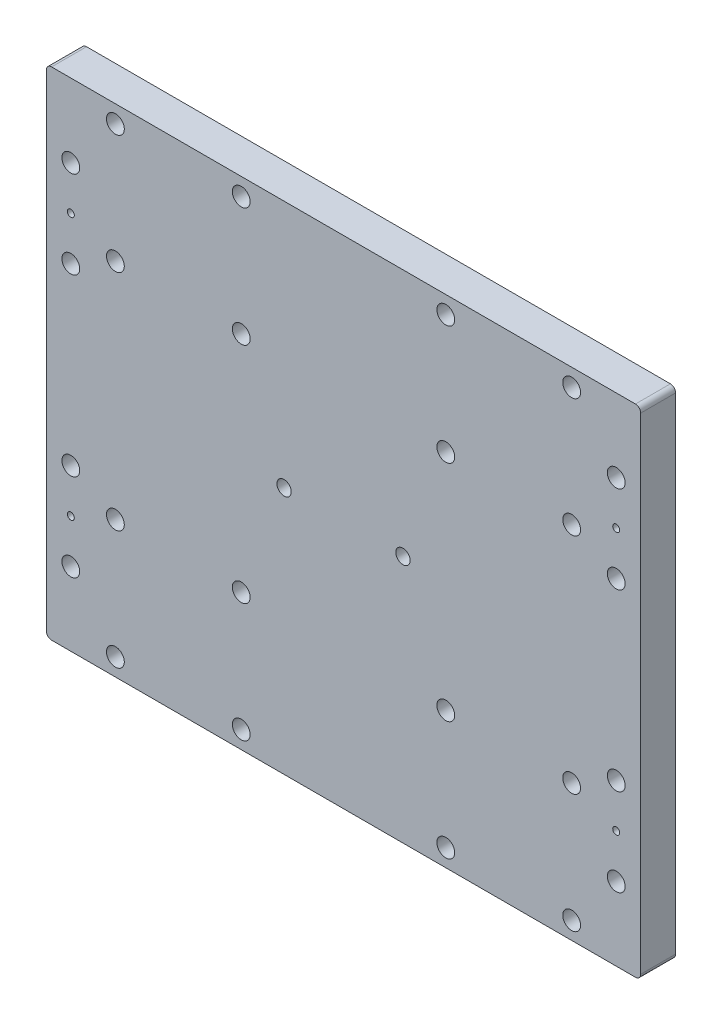
SolidWorks part; units mm, degrees
ref_plane "Front Plane" through (0, 0, 0) normal (0, 0, 1) x (1, 0, 0)
ref_plane "Top Plane" through (0, 0, 0) normal (0, 1, 0) x (1, 0, 0)
ref_plane "Right Plane" through (0, 0, 0) normal (1, 0, 0) x (0, 0, -1)
sketch "Sketch1" plane through (0, 0, 0) normal (0, 0, 1) x (1, 0, 0)
  line L1 (85, -71) -> (-85, -71)
  line L2 (85, -71) -> (85, 71)
  line L3 (85, 71) -> (-85, 71)
  line L4 (-85, -71) -> (-85, 71)
  line L5 (85, -71) -> (-85, 71) construction
  line L6 (85, 71) -> (-85, -71) construction
  point P0 (0, 0)
  dimension "D1" = 170
  dimension "D2" = 142
extrude "Boss-Extrude1" add sketch "Sketch1" along normal mid plane 10
sketch "Sketch2" plane through (0, 0, 5) normal (0, 0, 1) x (1, 0, 0)
  line L0 (-65.25, 71) -> (-65.25, -71) construction
  line L1 (65.25, -71) -> (65.25, 71) construction
  line L2 (-29.25, 71) -> (-29.25, -71) construction
  line L3 (29.25, -71) -> (29.25, 71) construction
  line L4 (70.6711, 66) -> (-71.3289, 66) construction
  line L5 (-71.3289, -66) -> (70.6711, -66) construction
  line L6 (70.6711, 32) -> (-71.3289, 32) construction
  line L7 (-71.3289, -32) -> (70.6711, -32) construction
  line L8 (85, 71) -> (-85, 71) construction
  line L9 (-85, -71) -> (85, -71) construction
  line L10 (-85, 71) -> (-85, -71) construction
  line L11 (85, -71) -> (85, 71) construction
  circle A0 centre (-65.25, 66) radius 2.55
  circle A1 centre (-29.25, 66) radius 2.55
  circle A2 centre (-29.25, 32) radius 2.55
  circle A3 centre (-65.25, 32) radius 2.55
  circle A4 centre (65.25, 66) radius 2.55
  circle A5 centre (65.25, 32) radius 2.55
  circle A6 centre (29.25, 32) radius 2.55
  circle A7 centre (29.25, 66) radius 2.55
  circle A8 centre (-65.25, -32) radius 2.55
  circle A9 centre (-29.25, -32) radius 2.55
  circle A10 centre (-29.25, -66) radius 2.55
  circle A11 centre (-65.25, -66) radius 2.55
  circle A12 centre (29.25, -32) radius 2.55
  circle A13 centre (65.25, -32) radius 2.55
  circle A14 centre (65.25, -66) radius 2.55
  circle A15 centre (29.25, -66) radius 2.55
  dimension "D1" = 5.1
  dimension "D2" = 5.1
  dimension "D3" = 5.1
  dimension "D4" = 5.1
  dimension "D5" = 5.1
  dimension "D6" = 5.1
  dimension "D7" = 5.1
  dimension "D8" = 5.1
  dimension "D9" = 5.1
  dimension "D10" = 5.1
  dimension "D11" = 5.1
  dimension "D12" = 5.1
  dimension "D13" = 5.1
  dimension "D14" = 5.1
  dimension "D15" = 5.1
  dimension "D16" = 5.1
  dimension "D17" = 5
  dimension "D18" = 5
  dimension "D19" = 34
  dimension "D20" = 34
  dimension "D21" = 36
  dimension "D22" = 36
  dimension "D23" = 19.75
  dimension "D24" = 19.75
extrude "Cut-Extrude1" cut sketch "Sketch2" against normal through all
sketch "Sketch4" plane through (0, 0, 5) normal (0, 0, 1) x (1, 0, 0)
  line L3 (-17, 0) -> (17, 0) construction
  circle A0 centre (-17, 0) radius 2.05
  circle A3 centre (17, 0) radius 2.05
  point P0 (0, 0)
  dimension "D3" = 4.1
  dimension "D4" = 4.1
  dimension "D1" = 34
extrude "Cut-Extrude3" cut sketch "Sketch4" against normal through all
fillet "Fillet1" radius 1.5 4 edges at (-85, -71, 0) (85, -71, 0) (85, 71, 0) (-85, 71, 0)
sketch "Sketch6" plane through (0, 0, 5) normal (0, 0, 1) x (1, 0, 0)
  line L0 (-78, -1002.1032) -> (-78, 48997.8968) construction
  line L1 (78, -1010.3548) -> (78, 48989.6452) construction
  line L2 (-85, 69.5) -> (-85, -69.5) construction
  line L3 (85, -69.5) -> (85, 69.5) construction
  line L6 (-1000, 0) -> (49000, 0) construction
  circle A0 centre (-78, 50) radius 2.55
  circle A1 centre (-78, 37.5) radius 1
  circle A2 centre (-78, 25) radius 2.55
  circle A3 centre (-78, -25) radius 2.55
  circle A4 centre (-78, -37.5) radius 1
  circle A5 centre (-78, -50) radius 2.55
  dimension "D3" = 5.1
  dimension "D4" = 2
  dimension "D5" = 5.1
  dimension "D6" = 5.1
  dimension "D7" = 5.1
  dimension "D8" = 2
  dimension "D9" = 25
  dimension "D12" = 25
  dimension "D14" = 50
  dimension "D11" = 50
  dimension "D1" = 7
  dimension "D2" = 7
  dimension "D10" = 37.5
  dimension "D13" = 37.5
extrude "Cut-Extrude5" cut sketch "Sketch6" against normal through all
mirror "Mirror1" about plane through (0, 0, 0) normal (1, 0, 0) of "Cut-Extrude5"
equation "\"D23@Sketch2\"=5.75+14"
equation "\"D24@Sketch2\"=5.75+14"
equation "\"D4@Sketch4\"=\"D3@Sketch4\""
equation "\"D5@Sketch6\" = \"D3@Sketch6\""
equation "\"D6@Sketch6\" = \"D3@Sketch6\""
equation "\"D7@Sketch6\"=\"D3@Sketch6\""
equation "\"D22@Sketch2\"=\"D21@Sketch2\""
equation "\"D20@Sketch2\"=\"D19@Sketch2\""
